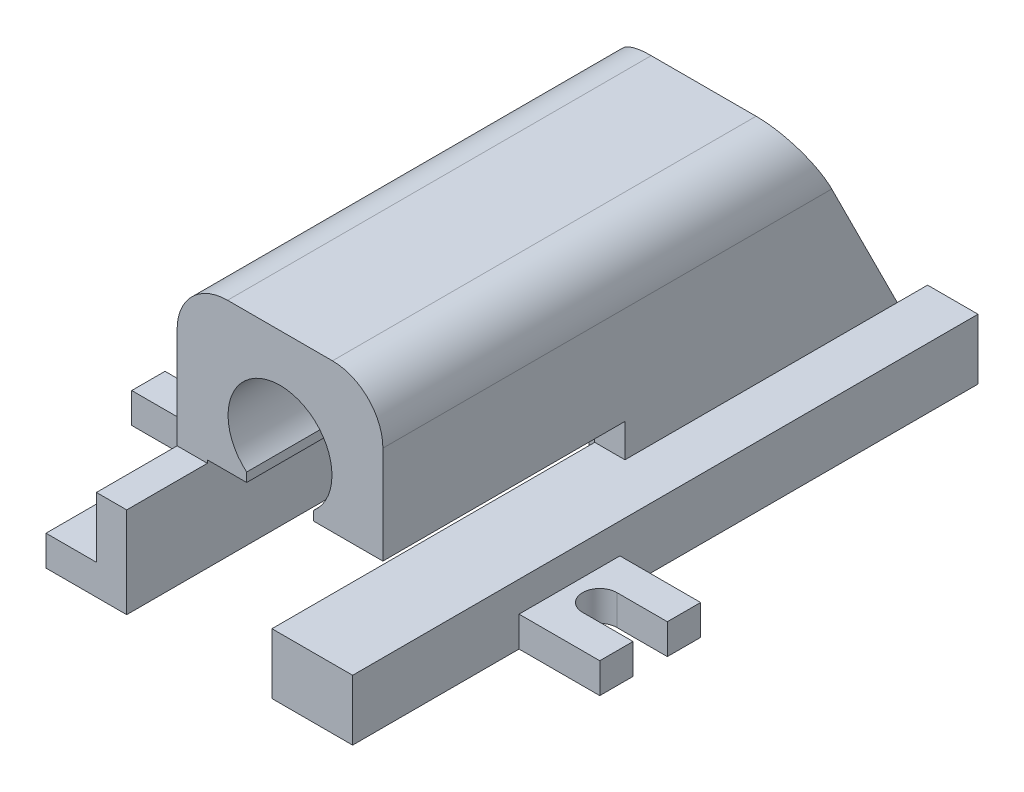
SolidWorks part; units mm, degrees
note: The reader was unsure of these and kept them because the rebuilt part matched: shared geometry of "Sketch15<6>".
ref_plane "Front Plane" through (0, 0, 0) normal (0, 0, 1) x (1, 0, 0)
ref_plane "Top Plane" through (0, 0, 0) normal (0, 1, 0) x (1, 0, 0)
ref_plane "Right Plane" through (0, 0, 0) normal (1, 0, 0) x (0, 0, -1)
sketch "Sketch1" plane through (0, 0, 0) normal (0, 1, 0) x (1, 0, 0)
  line L0 (0, -25.3554) -> (0, 0) construction
  line L1 (-15.2, -31) -> (-7.2, -31)
  line L2 (-15.2, -31) -> (-15.2, -14.5)
  line L3 (-15.2, 31) -> (15.2, 31)
  line L4 (15.2, -31) -> (15.2, -14.5)
  line L5 (-15.2, -31) -> (15.2, 31) construction
  line L6 (-15.2, 31) -> (15.2, -31) construction
  line L7 (7.2, -31) -> (15.2, -31)
  line L8 (-7.2, 26) -> (7.2, 26)
  line L9 (-7.2, 26) -> (-7.2, -31)
  line L11 (7.2, 26) -> (7.2, -31)
  line L12 (-7.2, 26) -> (7.2, -31) construction
  line L13 (-7.2, -31) -> (7.2, 26) construction
  line L14 (-18.2, -11.2) -> (-23.2, -11.2)
  line L17 (-15.2, -4.5) -> (-15.2, 31)
  line L22 (15.2, -4.5) -> (15.2, 31)
  line L23 (7.2, 5) -> (2.65, 5)
  line L24 (-7.2, 26) -> (-2.65, 26)
  line L25 (-7.2, 26) -> (-7.2, 5)
  line L26 (-7.2, 5) -> (-2.65, 5)
  line L27 (-2.65, 26) -> (-2.65, 5)
  line L28 (2.65, 26) -> (2.65, 5)
  line L29 (7.2, 26) -> (2.65, 26)
  line L30 (7.2, 26) -> (7.2, 5)
  line L31 (7.2, -9.5) -> (19.2, -9.5) construction
  line L32 (18.2, -9.5) -> (23.2, -9.5) construction
  line L33 (23.2, -14.5) -> (15.2, -14.5)
  line L34 (23.2, -14.5) -> (23.2, -4.5)
  line L35 (23.2, -4.5) -> (15.2, -4.5)
  line L37 (23.2, -14.5) -> (15.2, -4.5) construction
  line L38 (23.2, -4.5) -> (15.2, -14.5) construction
  line L39 (18.2, -7.8) -> (23.2, -7.8)
  line L40 (18.2, -11.2) -> (23.2, -11.2)
  line L41 (-18.2, -7.8) -> (-23.2, -7.8)
  line L44 (-23.2, -14.5) -> (-15.2, -14.5)
  line L45 (-23.2, -14.5) -> (-15.2, -4.5) construction
  line L46 (-23.2, -4.5) -> (-15.2, -14.5) construction
  line L47 (-23.2, -14.5) -> (-23.2, -11.2)
  line L48 (-23.2, -4.5) -> (-15.2, -4.5)
  line L49 (15.2, -4.5) -> (15.2, -14.5) construction
  line L50 (23.2, -7.8) -> (23.2, -11.2)
  line L52 (-23.2, -7.8) -> (-23.2, -4.5)
  arc A5 (18.2, -7.8) -> (18.2, -11.2) centre (18.2, -9.5) ccw
  arc A6 (-18.2, -7.8) -> (-18.2, -11.2) centre (-18.2, -9.5) cw
  point P0 (0, 0)
  point P8 (0, -2.5)
  point P27 (24.0579, -9.5)
  dimension "D5" = 3
  dimension "D8" = 2.65
  dimension "D13" = 1.7
  dimension "D1" = 14.4
  dimension "D2" = 57
  dimension "D3" = 5
  dimension "D4" = 8
  dimension "D9" = 36
  dimension "D10" = 21.5
  dimension "D11" = 8
  dimension "D12" = 10
extrude "Boss-Extrude1" add sketch "Sketch1" along normal blind 3 contours L11 L7 L4 L33 L34 L35 L22 L3 L17 L48 L52 L41 A6 L14 L47 L44 L2 L1 L9 L8 | L25 L24 L27 L26 | L30 L23 L28 L29 | L50 L40 A5 L39
fillet "Fillet1" radius 5 1 edges at (-15.2, 1.5, -31)
sketch "Sketch2" plane through (0, 0, -26) normal (0, 0, 1) x (1, 0, 0)
  line L0 (0, 0) -> (0, 3) construction
  line L1 (-2.65, 0) -> (2.65, 0) construction
  line L2 (-2.65, 3) -> (2.65, 3) construction
  line L4 (-2.5, 0) -> (2.5, 0)
  line L5 (-2.5, 0) -> (-2.5, 3)
  line L6 (-2.5, 3) -> (2.5, 3)
  line L7 (2.5, 0) -> (2.5, 3)
  line L8 (-2.5, 0) -> (2.5, 3) construction
  line L9 (-2.5, 3) -> (2.5, 0) construction
  point P6 (0, 1.5)
  dimension "D1" = 5
sketch "Sketch3" plane through (0, 3, 0) normal (0, 1, 0) x (1, 0, 0)
  line L6 (-10.2, 29) -> (-10.2, -31)
  line L7 (-10.2, 29) -> (10.2, 29)
  line L8 (10.2, 29) -> (10.2, -31)
  line L17 (-7.2, 26) -> (7.2, 26) construction
  line L18 (-7.2, 26) -> (-7.2, -31) construction
  line L19 (7.2, 26) -> (7.2, -31) construction
  line L20 (-2.65, 26) -> (2.65, 26)
  line L21 (-7.2, 5) -> (-7.2, -31)
  line L22 (7.2, 5) -> (7.2, -31)
  line L26 (-7.2, 5) -> (-2.65, 5) construction
  line L27 (-2.65, 26) -> (-2.65, 5) construction
  line L28 (7.2, 5) -> (2.65, 5) construction
  line L32 (2.65, 26) -> (2.65, 5) construction
  line L33 (-7.2, 5) -> (-2.65, 5)
  line L34 (-2.65, 26) -> (-2.65, 5)
  line L35 (7.2, 5) -> (2.65, 5)
  line L36 (2.65, 26) -> (2.65, 5)
  line L37 (-7.2, 26) -> (7.2, 26) construction
  line L38 (-7.2, 26) -> (-7.2, -31) construction
  line L39 (7.2, 26) -> (7.2, -31) construction
  line M11 (-15.2, -31) -> (-7.2, -31)
  line M12 (-7.2, -31) -> (-7.2, 5)
  line M13 (-2.65, 26) -> (2.65, 26)
  line M14 (7.2, 5) -> (7.2, -31)
  line M15 (7.2, -31) -> (15.2, -31)
  dimension "D1" = 3
extrude "Boss-Extrude2" add sketch "Sketch3" along normal blind 6 contours L20 L22 L8 L7 L6 L21 M14 M15 M11 M12 M13
sketch "Sketch9" plane through (0, 9, 0) normal (0, 1, 0) x (1, 0, 0)
  line L0 (0, 0) -> (0, 29) construction
  line L3 (-10.2, -23) -> (-10.2, 29)
  line L4 (-10.2, 29) -> (10.2, 29)
  line L5 (10.2, -23) -> (10.2, 29)
  line L6 (-10.2, -23) -> (10.2, 29) construction
  line L7 (-10.2, 29) -> (10.2, -23) construction
  line L8 (0, 0) -> (0, -23) construction
  line L10 (-10.2, -23) -> (10.2, -23)
  line L11 (7.2, -31) -> (10.2, -31) construction
  point P3 (0, 3)
  dimension "D1" = 8
extrude "Boss-Extrude4" add sketch "Sketch9" along normal blind 15
sketch "Sketch15" plane through (0, 0, 23) normal (0, 0, 1) x (1, 0, 0)
  line L0 (0, 9) -> (0, 24) construction
  line L1 (-7.2, 9) -> (7.2, 9) construction
  line L2 (-10.2, 24) -> (10.2, 24) construction
  line L3 (-3.3045, 10.2) -> (-3.3045, 9.3)
  line L4 (3.3045, 10.2) -> (3.3045, 9.3)
  line L5 (-3.3045, 9) -> (3.3045, 9)
  line L6 (-7.2, 9) -> (-7.2, 0) construction
  line L7 (7.2, 9) -> (7.2, 0) construction
  line L8 (-7.2, 9) -> (-7.2, 0)
  line L9 (7.2, 9) -> (7.2, 0)
  line L10 (-3.3045, 9.3) -> (-7.2, 9.3)
  line L11 (7.2, 9) -> (-7.2, 9)
  line L12 (7.2, 9) -> (7.2, 9.3)
  line L13 (7.2, 9.3) -> (3.3045, 9.3)
  line L14 (-7.2, 9) -> (-7.2, 9.3)
  arc A0 (3.3045, 10.2) -> (-3.3045, 10.2) centre (0, 14.15) ccw
  circle A1 centre (0, 14.15) radius 1.5
  line M3 (-7.2, 9) -> (7.2, 9)
  dimension "D1" = 10.3
  dimension "D4" = 3
  dimension "D2" = 1.2
  dimension "D3" = 0.3
chamfer "Chamfer4" distance 20 distance2 10 1 edges at (0, 24, -29)
fillet "Fillet5" radius 5 2 edges at (10.2, 24, 2) (-10.2, 24, 2)
extrude "Cut-Extrude6" cut sketch "Sketch15" against normal up to surface (28 mm away) contours L0 A0 L3 L10 L14 M3 | L0 L11 L12 L13 L4 A0 M3 | A1
extrude "Cut-Extrude7" cut sketch "Sketch15<6>" against normal through all contours L0 A1 | A1 L0
sketch "Sketch15<6>" plane through (0, 0, 23) normal (0, 0, 1) x (1, 0, 0) same geometry as "Sketch15"
sketch "Sketch16" plane through (10.2, 0, 0) normal (1, 0, 0) x (0, 0, -1)
  line L0 (-31, 9) -> (-31, 3) construction
  line L1 (-31, 6) -> (1, 6)
  line L2 (-31, 6) -> (-31, 9.3)
  line L3 (-31, 9.3) -> (1, 9.3)
  line L4 (1, 6) -> (1, 9.3)
  line L5 (-23, 9) -> (-31, 9) construction
  point P6 (0, 0)
  dimension "D1" = 0.3
  dimension "D2" = 3
  dimension "D3" = 32
extrude "Cut-Extrude8" cut sketch "Sketch16" against normal up to surface (3 mm away) up to face at (7.2, 6.1, 16.3333)
sketch "Sketch17" plane through (0, 3, 0) normal (0, 1, 0) x (1, 0, 0)
  line L0 (-15.2, 31) -> (15.2, 31) construction
  line L1 (15.2, -31) -> (10.2, -31)
  line L2 (15.2, -31) -> (15.2, 31)
  line L3 (15.2, 31) -> (10.2, 31)
  line L4 (10.2, -31) -> (10.2, 31)
  line L5 (10.2, 29) -> (10.2, -31) construction
extrude "Boss-Extrude5" add sketch "Sketch17" along normal up to surface (3 mm away) up to face at (8.7, 6, 15)
